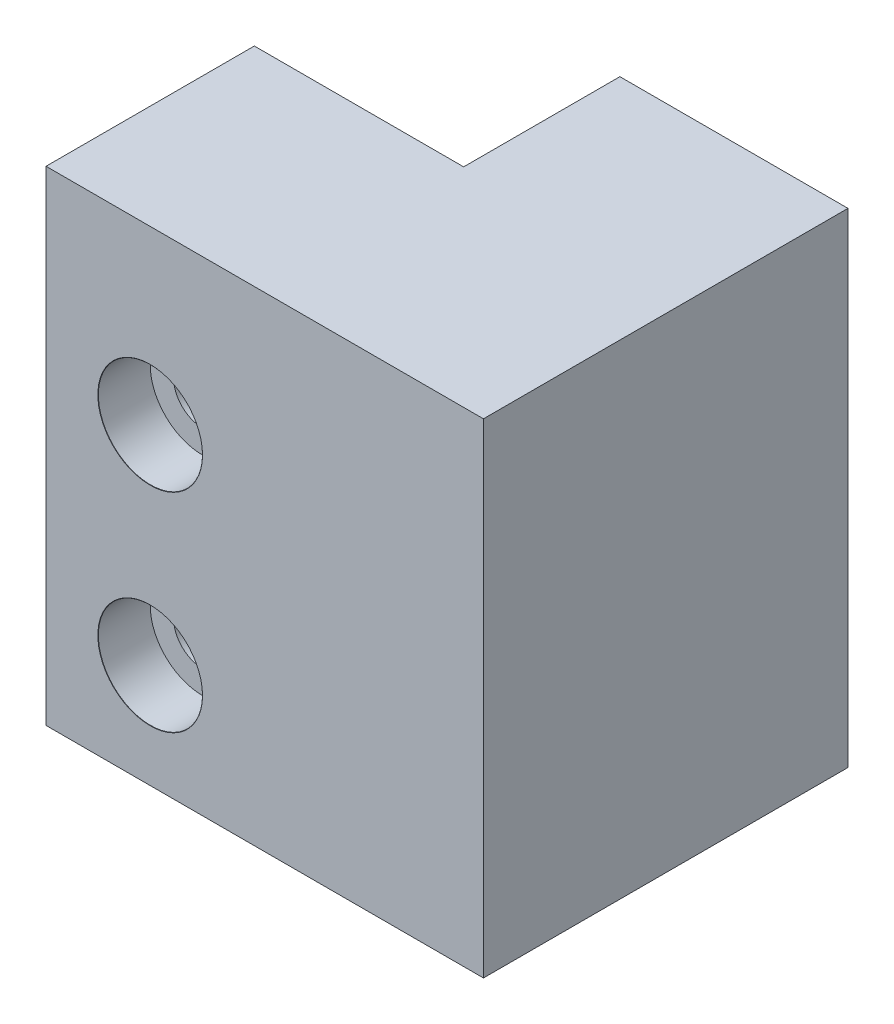
SolidWorks part; units mm, degrees
ref_plane "Front Plane" through (0, 0, 0) normal (0, 0, 1) x (1, 0, 0)
ref_plane "Top Plane" through (0, 0, 0) normal (0, 1, 0) x (1, 0, 0)
ref_plane "Right Plane" through (0, 0, 0) normal (1, 0, 0) x (0, 0, -1)
sketch "Sketch1" plane through (0, 0, 0) normal (0, 1, 0) x (1, 0, 0)
  line L1 (21, 10) -> (-21, 10)
  line L2 (21, 10) -> (21, -10)
  line L3 (21, -10) -> (-21, -10)
  line L4 (-21, 10) -> (-21, -10)
  line L5 (21, 10) -> (-21, -10) construction
  line L6 (21, -10) -> (-21, 10) construction
  point P0 (0, 0)
  dimension "D1" = 42
  dimension "D2" = 20
extrude "Boss-Extrude1" add sketch "Sketch1" along normal blind 40
sketch "Sketch2" plane through (0, 40, 0) normal (0, 1, 0) x (1, 0, 0)
  line L0 (-21, 10) -> (-21, -10) construction
  line L1 (21, 10) -> (-0.9, 10)
  line L2 (21, 10) -> (21, 25)
  line L3 (21, 25) -> (-0.9, 25)
  line L4 (-0.9, 10) -> (-0.9, 25)
  dimension "D1" = 15
  dimension "D2" = 20.1
extrude "Boss-Extrude2" add sketch "Sketch2" against normal up to surface (40 mm away) up to face at (0, 0, 0)
sketch "Sketch3" plane through (0, 0, 10) normal (0, 0, 1) x (1, 0, 0)
  line L0 (-21, 20) -> (21, 20) construction
  line L1 (-21, 40) -> (-21, 0) construction
  line L2 (21, 40) -> (21, 0) construction
  line L3 (-11, 30) -> (-11, 10)
  point P9 (-11, 20)
  dimension "D1" = 20
  dimension "D2" = 10
hole_wizard "CBORE for M5 SHCS1" positions "Sketch4" profile "Sketch5" counterbore size "M5" standard "ANSI Metric" end condition through all
sketch "Sketch4" plane through (0, 0, 10) normal (0, 0, 1) x (1, 0, 0)
  point P0 (-11, 30)
  point P3 (-11, 10)
sketch "Sketch5" plane through (-11, 30, 10) normal (1, 0, 0) x (0, -1, 0)
  line L0 (0, 0) -> (0, 35)
  line L1 (0, 35) -> (2.75, 35)
  line L3 (2.75, 35) -> (2.75, 5)
  line L4 (5, 5) -> (2.75, 5)
  line L5 (5, 5) -> (5, 0.021)
  line L6 (5, 0.021) -> (5.025, 0)
  line L7 (5.025, 0) -> (0, 0)
  line L8 (-5, 0.021) -> (-5.025, 0) construction
  line L11 (0, -6.35) -> (0, 107.95) construction
  dimension "Thru Hole Dia." = 5.5
  dimension "Thru Hole Depth" = 35
  dimension "C'Bore Dia." = 10
  dimension "C'Bore Depth" = 5
  dimension "Near C'Sink Dia." = 10.05
  dimension "Near C'Sink Angle" = 100
sketch "Sketch6" plane through (0, 40, 0) normal (0, 1, 0) x (1, 0, 0)
  line L6 (-21, 10) -> (-21, -10)
  line L7 (-21, -10) -> (21, -10)
  line L8 (21, -10) -> (21, 25)
  line L9 (21, 25) -> (-0.9, 25)
  line L10 (-0.9, 25) -> (-0.9, 10)
  line L11 (-0.9, 10) -> (-21, 10)
  line L12 (-21, 10) -> (-21, -10)
  line L13 (-21, -10) -> (21, -10)
  line L14 (21, -10) -> (21, 25)
  line L15 (21, 25) -> (-0.9, 25)
  line L16 (-0.9, 25) -> (-0.9, 10)
  line L17 (-0.9, 10) -> (-21, 10)
  dimension "D1" = 0
extrude "Boss-Extrude3" add sketch "Sketch6" along normal blind 6.5
sketch "Sketch7" plane through (0, 46.5, 0) normal (0, 1, 0) x (1, 0, 0)
  line L0 (16.51, 25) -> (16.51, -2.5123)
  line L1 (21, 25) -> (-0.9, 25) construction
  line L2 (21, -10) -> (21, 25) construction
  dimension "D1" = 4.49
